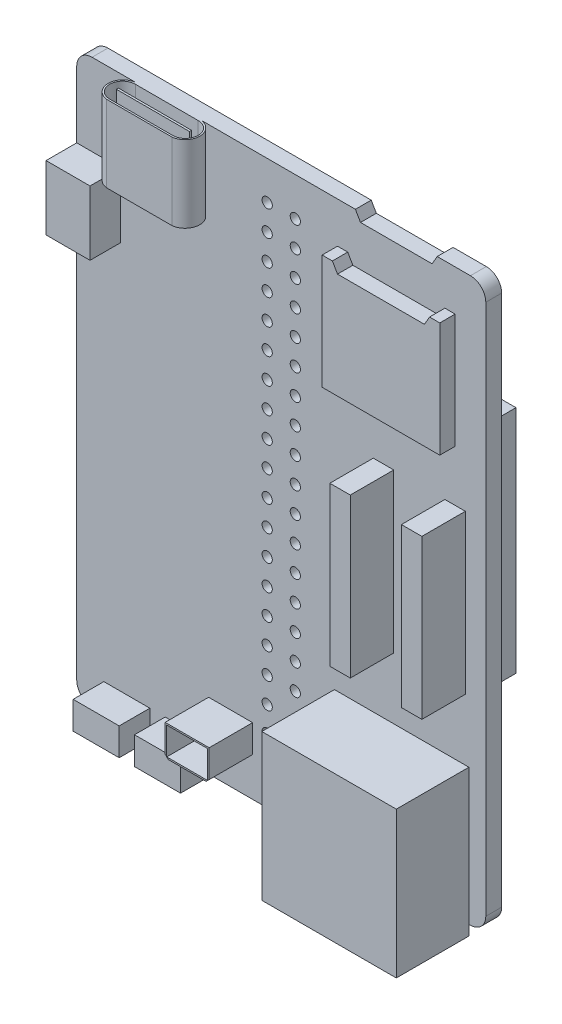
SolidWorks part; units mm, degrees
ref_plane "Front Plane" through (0, 0, 0) normal (1, 0, 0) x (0, 1, 0)
ref_plane "Top Plane" through (0, 0, 0) normal (0, 0, 1) x (0, 1, 0)
ref_plane "Right Plane" through (0, 0, 0) normal (0, 1, 0) x (-1, 0, 0)
sketch "Sketch1" plane through (0, 0, 0) normal (0, 0, 1) x (0, 1, 0)
  line L1 (-27.5, -20) -> (27.5, -20)
  line L2 (-27.5, -20) -> (-27.5, 20)
  line L3 (-27.5, 20) -> (27.5, 20)
  line L4 (27.5, -20) -> (27.5, 20)
  line L5 (-27.5, -20) -> (27.5, 20) construction
  line L6 (-27.5, 20) -> (27.5, -20) construction
  point P0 (0, 0)
  dimension "D1" = 55
  dimension "D2" = 40
extrude "Boss-Extrude1" add sketch "Sketch1" along normal blind 1.55
fillet "Fillet1" radius 1.5 4 edges at (-20, 27.5, 0.775) (-20, -27.5, 0.775) (20, 27.5, 0.775) (20, -27.5, 0.775)
sketch "Sketch2" plane through (0, 0, 1.55) normal (0, 0, 1) x (1, 0, 0)
  line L0 (20, -26) -> (20, 26) construction
  line L1 (5.2, -14.2) -> (18.35, -14.2)
  line L2 (5.2, -14.2) -> (5.2, -28.5)
  line L3 (5.2, -28.5) -> (18.35, -28.5)
  line L4 (18.35, -14.2) -> (18.35, -28.5)
  line L5 (5.2, -14.2) -> (18.35, -28.5) construction
  line L6 (5.2, -28.5) -> (18.35, -14.2) construction
  line L7 (-18.5, -27.5) -> (18.5, -27.5) construction
  point P0 (11.775, -21.35)
  dimension "D1" = 1.65
  dimension "D2" = 1
  dimension "D3" = 14.3
  dimension "D4" = 13.15
extrude "Boss-Extrude2" add sketch "Sketch2" along normal blind 7.1
sketch "Sketch3" plane through (0, -28.5, 0) normal (0, -1, 0) x (1, 0, 0)
  line L0 (5.2, 8.65) -> (18.35, 8.65) construction
  line L1 (5.525, 1.85) -> (18.025, 1.85)
  line L2 (5.525, 1.85) -> (5.525, 8.35)
  line L3 (5.525, 8.35) -> (18.025, 8.35)
  line L4 (18.025, 1.85) -> (18.025, 8.35)
  line L5 (5.525, 1.85) -> (18.025, 8.35) construction
  line L6 (5.525, 8.35) -> (18.025, 1.85) construction
  line L7 (5.2, 8.65) -> (18.35, 8.65)
  line L8 (18.35, 8.65) -> (18.35, 1.55) construction
  line L9 (18.35, 8.65) -> (18.35, 1.55)
  line L10 (11.775, 8.65) -> (11.775, 2.4652) construction
  line L11 (18.35, 5.1) -> (11.2496, 5.1) construction
  line L13 (6.225, 6.85) -> (17.325, 6.85)
  line L14 (6.225, 6.85) -> (6.225, 5.3523)
  line L15 (6.225, 5.3523) -> (17.325, 5.3523)
  line L16 (17.325, 6.85) -> (17.325, 5.3523)
  line L17 (5.525, 6.1356) -> (5.2, 6.1356) construction
  line L18 (5.2, 8.65) -> (5.2, 1.55) construction
  line L19 (18.025, 6.1356) -> (18.35, 6.1356) construction
  point P0 (11.775, 5.1)
  point P12 (11.775, 5.1)
  point P23 (17.0651, 5.3523)
  dimension "D1" = 12.5
  dimension "D2" = 6.5
  dimension "D3" = 1.5
  dimension "D5" = 0.7
  dimension "D6" = 1.4977
extrude "Cut-Extrude1" cut sketch "Sketch3" against normal offset from surface (13.3 mm away) 1 contours L1 L4 L3 L2 L13 L16 L15 L14 region at (11.775, -28.5, 4.8425) up to face at (11.775, -14.2, 5.1)
sketch "Sketch4" plane through (0, 0, 1.55) normal (0, 0, 1) x (1, 0, 0)
  line L0 (18.5, 27.5) -> (-18.5, 27.5) construction
  line L1 (-15.5, 27.5) -> (-6.55, 27.5)
  line L2 (-15.5, 27.5) -> (-15.5, 20)
  line L3 (-15.5, 20) -> (-6.55, 20)
  line L4 (-6.55, 27.5) -> (-6.55, 20)
  line L5 (-20, 26) -> (-20, -26) construction
  dimension "D1" = 4.5
  dimension "D2" = 7.5
  dimension "D3" = 8.95
extrude "Boss-Extrude3" add sketch "Sketch4" along normal blind 2.85
sketch "Sketch5" plane through (0, 27.5, 0) normal (0, 1, 0) x (-1, 0, 0)
  line L0 (6.55, 4.4) -> (15.5, 4.4) construction
  line L1 (6.55, 4.4) -> (15.5, 4.4) construction
  line L2 (6.55, 1.55) -> (15.5, 1.55) construction
  line L4 (11.025, 4.4) -> (11.025, 1.9427) construction
  line L7 (7.8105, 1.55) -> (6.55, 1.55)
  line L8 (6.55, 1.55) -> (6.55, 4.4)
  line L9 (6.55, 4.4) -> (7.8105, 4.4)
  line L10 (6.55, 4.4) -> (7.8105, 4.4)
  line L11 (14.2395, 4.4) -> (15.5, 4.4)
  line L12 (15.5, 4.4) -> (15.5, 2.975)
  line L13 (15.5, 2.975) -> (15.5, 1.55)
  line L14 (15.5, 1.55) -> (14.2395, 1.55)
  line L15 (7.95, 2.975) -> (14.1, 2.975) construction
  line L16 (7.95, 4.2305) -> (14.1, 4.2305)
  line L17 (7.95, 1.7195) -> (14.1, 1.7195)
  line L19 (7.45, 2.875) -> (14.6, 2.875)
  line L20 (7.45, 2.875) -> (7.45, 3.075)
  line L21 (7.45, 3.075) -> (14.6, 3.075)
  line L22 (14.6, 2.875) -> (14.6, 3.075)
  line L23 (7.45, 2.875) -> (14.6, 3.075) construction
  line L24 (7.45, 3.075) -> (14.6, 2.875) construction
  arc A0 (7.8105, 1.55) -> (7.8105, 4.4) centre (7.9857, 2.975) cw
  arc A1 (14.2395, 1.55) -> (14.2395, 4.4) centre (14.0643, 2.975) ccw
  arc A2 (7.95, 4.2305) -> (7.95, 1.7195) centre (7.95, 2.975) ccw
  arc A3 (14.1, 1.7195) -> (14.1, 4.2305) centre (14.1, 2.975) ccw
  point P17 (11.025, 2.975)
  point P22 (11.025, 2.975)
  line M7 (15.5, 1.55) -> (15.5, 4.4)
  line M8 (15.5, 4.4) -> (6.55, 4.4)
  line M9 (6.55, 4.4) -> (6.55, 1.55)
  dimension "D1" = 1.4357
  dimension "D2" = 6.15
  dimension "D3" = 1.2555
  dimension "D4" = 7.15
  dimension "D5" = 0.2
extrude "Cut-Extrude2" cut sketch "Sketch5" against normal up to surface (7.5 mm away) contours A0 M9 M8 | L7 A0 L8 | A1 L14 M7 | A1 M7 M8 region at (-15.1905, 27.5, 1.8704) region at (-15.1905, 27.5, 4.0796) region at (-6.8595, 27.5, 4.0796) region at (-6.8595, 27.5, 1.8704) up to face at (-11.025, 20, 2.975)
extrude "Cut-Extrude3" cut sketch "Sketch5<3>" against normal offset from surface (7 mm away) 0.5 contours L17 A3 L16 A2 L22 L19 L20 L21 region at (-11.025, 27.5, 4.1404) up to face at (-11.025, 20, 2.975)
sketch "Sketch5<3>" plane through (0, 27.5, 0) normal (0, 1, 0) x (-1, 0, 0) same geometry as "Sketch5"
sketch "Sketch6" plane through (0, 0, 1.55) normal (0, 0, 1) x (1, 0, 0)
  line L0 (16, 23.5) -> (15.5, 22.634)
  line L1 (17, 12.3) -> (5.5, 12.3)
  line L2 (17, 12.3) -> (17, 23.5)
  line L3 (17, 23.5) -> (16, 23.5)
  line L4 (5.5, 12.3) -> (5.5, 23.5)
  line L5 (18.35, -28.5) -> (18.35, -14.2) construction
  line L6 (18.35, -28.5) -> (18.35, -14.2) construction
  line L7 (15.5, 22.634) -> (7, 22.634)
  line L8 (7, 22.634) -> (6.5, 23.5)
  line L9 (6.5, 23.5) -> (5.5, 23.5)
  line L10 (18.5, 27.5) -> (-7.8105, 27.5) construction
  line L12 (20, -26) -> (20, 26) construction
  dimension "D1" = 120
  dimension "D2" = 8.5
  dimension "D3" = 3
  dimension "D4" = 1
  dimension "D5" = 11.5
  dimension "D6" = 11.2
  dimension "D7" = 4
extrude "Boss-Extrude4" add sketch "Sketch6" along normal blind 1.5
sketch "Sketch7" plane through (0, 0, 1.55) normal (0, 0, 1) x (1, 0, 0)
  line L3 (16, 23.5) -> (15.5, 22.634) construction
  line L5 (7, 22.634) -> (6.5, 23.5) construction
  line L6 (15.5, 22.634) -> (7, 22.634) construction
  line L7 (16, 23.5) -> (15.5, 22.634) construction
  line L8 (7, 22.634) -> (6.5, 23.5) construction
  line L9 (15.5, 22.634) -> (7, 22.634) construction
  line L10 (7.25, 27.5) -> (7.75, 26.634)
  line L11 (18.5, 27.5) -> (-7.8105, 27.5) construction
  line L12 (15.25, 27.5) -> (14.75, 26.634)
  line L13 (7.75, 26.634) -> (14.75, 26.634)
  line L14 (7.25, 27.5) -> (15.25, 27.5)
  point P10 (11.25, 26.634)
  point P11 (11.25, 22.634)
  dimension "D1" = 7
  dimension "D2" = 120
extrude "Cut-Extrude4" cut sketch "Sketch7" against normal blind 10
sketch "Sketch8" plane through (0, 0, 1.55) normal (0, 0, 1) x (1, 0, 0)
  line L0 (-18.5, -27.5) -> (5.2, -27.5) construction
  line L1 (-17.35, -27.5) -> (-12.85, -27.5)
  line L2 (-17.35, -27.5) -> (-17.35, -24.8)
  line L3 (-17.35, -24.8) -> (-12.85, -24.8)
  line L4 (-12.85, -27.5) -> (-12.85, -24.8)
  line L5 (-20, 26) -> (-20, -26) construction
  line L6 (-12.1, -27.5) -> (-12.1, -22.0575) construction
  line L7 (-6.85, -24.8) -> (-11.35, -24.8)
  line L8 (-11.35, -27.5) -> (-11.35, -24.8)
  line L9 (-6.85, -27.5) -> (-11.35, -27.5)
  line L10 (-6.85, -27.5) -> (-6.85, -24.8)
  line L12 (-7.1, -21) -> (-2.8, -21)
  line L13 (-7.1, -21) -> (-7.1, -24)
  line L14 (-7.1, -24) -> (-2.8, -24)
  line L15 (-2.8, -21) -> (-2.8, -24)
  line M20 (-18.5, -27.5) -> (5.2, -27.5)
  dimension "D1" = 4.5
  dimension "D2" = 2.7
  dimension "D3" = 13.15
  dimension "D4" = 1.5
  dimension "D5" = 12.9
  dimension "D6" = 3.5
  dimension "D7" = 3
  dimension "D8" = 4.3
extrude "Boss-Extrude5" add sketch "Sketch8" along normal blind 3 contours L10 L7 L8 M20 | L4 L3 L2 M20 region at (-15.1, -26.15, 1.55) region at (-9.1, -26.15, 1.55)
sketch "Sketch9" plane through (0, -27.5, 0) normal (0, -1, 0) x (1, 0, 0)
  line L0 (-12.1, 3.8788) -> (-12.1, 2.2212) construction
  line L1 (-11.35, 4.55) -> (-11.35, 1.55) construction
  line L2 (-12.85, 4.55) -> (-12.85, 1.55) construction
  line L3 (-17.35, 4.55) -> (-17.35, 1.55) construction
  line L5 (-12.1, 3.05) -> (-12.85, 3.05) construction
  line L6 (-11.35, 4.55) -> (-11.35, 1.55) construction
  line L7 (-12.85, 4.55) -> (-12.85, 1.55) construction
  line L8 (-17.35, 4.55) -> (-17.35, 1.55) construction
  line L9 (-17.35, 4.55) -> (-12.85, 4.55) construction
  line L10 (-12.1, 3.05) -> (-11.35, 3.05) construction
  line L11 (-17.35, 4.55) -> (-12.85, 4.55) construction
  line L13 (-15.1, 4.55) -> (-15.1, 1.55) construction
  circle A0 centre (-15.1, 3.05) radius 1
  circle A1 centre (-9.1, 3.05) radius 1
  point P10 (-12.85, 3.05)
  dimension "D1" = 2
extrude "Boss-Extrude6" add sketch "Sketch9" along normal blind 0.5 contours A1 | A0 region at (-9.1, -27.5, 3.05)
sketch "Sketch10" plane through (0, 0, 1.55) normal (0, 0, 1) x (1, 0, 0)
  line L0 (17, 12.3) -> (17, 23.5) construction
  line L1 (17, 12.3) -> (17, 23.5) construction
  line L2 (18.35, -14.2) -> (5.2, -14.2) construction
  line L3 (18, 7.3) -> (16, 7.3)
  line L4 (18, 7.3) -> (18, -8.2)
  line L5 (18, -8.2) -> (16, -8.2)
  line L6 (16, 7.3) -> (16, -8.2)
  line L8 (13.5, 8.7091) -> (13.5, -10.2301) construction
  line L9 (9, -8.2) -> (11, -8.2)
  line L10 (11, 7.3) -> (11, -8.2)
  line L11 (9, 7.3) -> (11, 7.3)
  line L12 (9, 7.3) -> (9, -8.2)
  line L13 (20, -26) -> (20, 26) construction
  dimension "D1" = 15.5
  dimension "D2" = 2
  dimension "D3" = 6
  dimension "D4" = 5
  dimension "D5" = 2
extrude "Boss-Extrude7" add sketch "Sketch10" along normal blind 4.25
extrude "Boss-Extrude9" add sketch "Sketch8<4>" along normal blind 4.25 separate body contours L15 L12 L13 L14 region at (-4.95, -22.5, 1.55)
sketch "Sketch8<4>" plane through (0, 0, 1.55) normal (0, 0, 1) x (1, 0, 0) same geometry as "Sketch8"
shell "Shell2" thickness 0.15 removed face at (-4.95, -22.5, 5.8)
combine bodies "Combine1" operation type add bodies to combine 111 113
chamfer "Chamfer1" distance 0.3 angle 45 2 edges at (-7.1, -24, 3.675) (-2.8, -24, 3.675) tangent propagation no
sketch "Sketch11" plane through (0, 0, 1.55) normal (0, 0, 1) x (1, 0, 0)
  line L0 (7.25, 27.5) -> (-7.8105, 27.5) construction
  line L1 (2.75, -25.5) -> (-2.75, -25.5) construction
  line L2 (2.75, -25.5) -> (2.75, 25.5) construction
  line L3 (2.75, 25.5) -> (-2.75, 25.5) construction
  line L4 (-2.75, -25.5) -> (-2.75, 25.5) construction
  line L5 (-6.85, -27.5) -> (5.2, -27.5) construction
  line L6 (-14.2395, 27.5) -> (-18.5, 27.5) construction
  line L10 (2.75, 0) -> (20, 0) construction
  line L11 (20, -26) -> (20, 26) construction
  line L12 (-2.75, 0) -> (-20, 0) construction
  line L13 (-20, 26) -> (-20, -26) construction
  line L16 (0, 25.5) -> (0, -25.5) construction
  line L17 (0, 23.75) -> (1.375, 23.75) construction
  line L18 (1.375, 23.75) -> (2.75, 23.75) construction
  line L19 (1.375, 23.75) -> (1.375, 25.5) construction
  line L20 (1.375, -23.75) -> (1.375, -25.5) construction
  circle A0 centre (1.375, 23.75) radius 0.5
  circle A1 centre (1.375, 21.25) radius 0.5
  circle A2 centre (1.375, 18.75) radius 0.5
  circle A3 centre (1.375, 16.25) radius 0.5
  circle A4 centre (1.375, 13.75) radius 0.5
  circle A5 centre (1.375, 11.25) radius 0.5
  circle A6 centre (1.375, 8.75) radius 0.5
  circle A7 centre (1.375, 6.25) radius 0.5
  circle A8 centre (1.375, 3.75) radius 0.5
  circle A9 centre (1.375, 1.25) radius 0.5
  circle A10 centre (1.375, -1.25) radius 0.5
  circle A11 centre (1.375, -3.75) radius 0.5
  circle A12 centre (1.375, -6.25) radius 0.5
  circle A13 centre (1.375, -8.75) radius 0.5
  circle A14 centre (1.375, -11.25) radius 0.5
  circle A15 centre (1.375, -13.75) radius 0.5
  circle A16 centre (1.375, -16.25) radius 0.5
  circle A17 centre (1.375, -18.75) radius 0.5
  circle A18 centre (1.375, -21.25) radius 0.5
  circle A19 centre (1.375, -23.75) radius 0.5
  circle A20 centre (-1.375, -23.75) radius 0.5
  circle A21 centre (-1.375, -21.25) radius 0.5
  circle A22 centre (-1.375, -18.75) radius 0.5
  circle A23 centre (-1.375, -16.25) radius 0.5
  circle A24 centre (-1.375, -13.75) radius 0.5
  circle A25 centre (-1.375, -11.25) radius 0.5
  circle A26 centre (-1.375, -8.75) radius 0.5
  circle A27 centre (-1.375, -6.25) radius 0.5
  circle A28 centre (-1.375, -3.75) radius 0.5
  circle A29 centre (-1.375, -1.25) radius 0.5
  circle A30 centre (-1.375, 1.25) radius 0.5
  circle A31 centre (-1.375, 3.75) radius 0.5
  circle A32 centre (-1.375, 6.25) radius 0.5
  circle A33 centre (-1.375, 8.75) radius 0.5
  circle A34 centre (-1.375, 11.25) radius 0.5
  circle A35 centre (-1.375, 13.75) radius 0.5
  circle A36 centre (-1.375, 16.25) radius 0.5
  circle A37 centre (-1.375, 18.75) radius 0.5
  circle A38 centre (-1.375, 23.75) radius 0.5
  circle A39 centre (-1.375, 21.25) radius 0.5
  point P105 (-16.3697, 27.5)
  dimension "D5" = 1
  dimension "D1" = 5.5
  dimension "D2" = 2
  dimension "D3" = 2
  dimension "D4" = 51
  dimension "D6" = 20
  dimension "D7" = 2.5
  dimension "D8" = 27.5
extrude "Cut-Extrude5" cut sketch "Sketch11" against normal up to next (1.55 mm away)
sketch "Sketch12" plane through (0, 0, 1.55) normal (0, 0, 1) x (1, 0, 0)
  line L0 (-20, 26) -> (-20, -26) construction
  line L1 (-20, 19.5) -> (-15.7, 19.5)
  line L2 (-20, 19.5) -> (-20, 13.2)
  line L3 (-20, 13.2) -> (-15.7, 13.2)
  line L4 (-15.7, 19.5) -> (-15.7, 13.2)
  line L5 (-14.2395, 27.5) -> (-18.5, 27.5) construction
  dimension "D1" = 6.3
  dimension "D2" = 4.3
  dimension "D3" = 8
extrude "Boss-Extrude10" add sketch "Sketch12" along normal blind 3 separate body
shell "Shell3" thickness 0.2 removed face at (-20, 16.35, 3.05)
sketch "Sketch13" plane through (0, 0, 0) normal (0, 0, -1) x (1, 0, 0)
  line L0 (18.5, -27.5) -> (15.25, -27.5) construction
  line L1 (15.5, 8.5) -> (18.4, 8.5)
  line L2 (15.5, 8.5) -> (15.5, -14)
  line L3 (15.5, -14) -> (18.4, -14)
  line L4 (18.4, 8.5) -> (18.4, -14)
  line L6 (-20, -26) -> (-20, 26) construction
  line L8 (0, 0) -> (0, -6.8775) construction
  line L9 (-15.5, -14) -> (-18.4, -14)
  line L10 (-18.4, 8.5) -> (-18.4, -14)
  line L11 (-15.5, 8.5) -> (-18.4, 8.5)
  line L12 (-15.5, 8.5) -> (-15.5, -14)
  dimension "D1" = 13.5
  dimension "D2" = 2.9
  dimension "D3" = 22.5
  dimension "D4" = 35.5
extrude "Boss-Extrude11" add sketch "Sketch13" along normal blind 3
